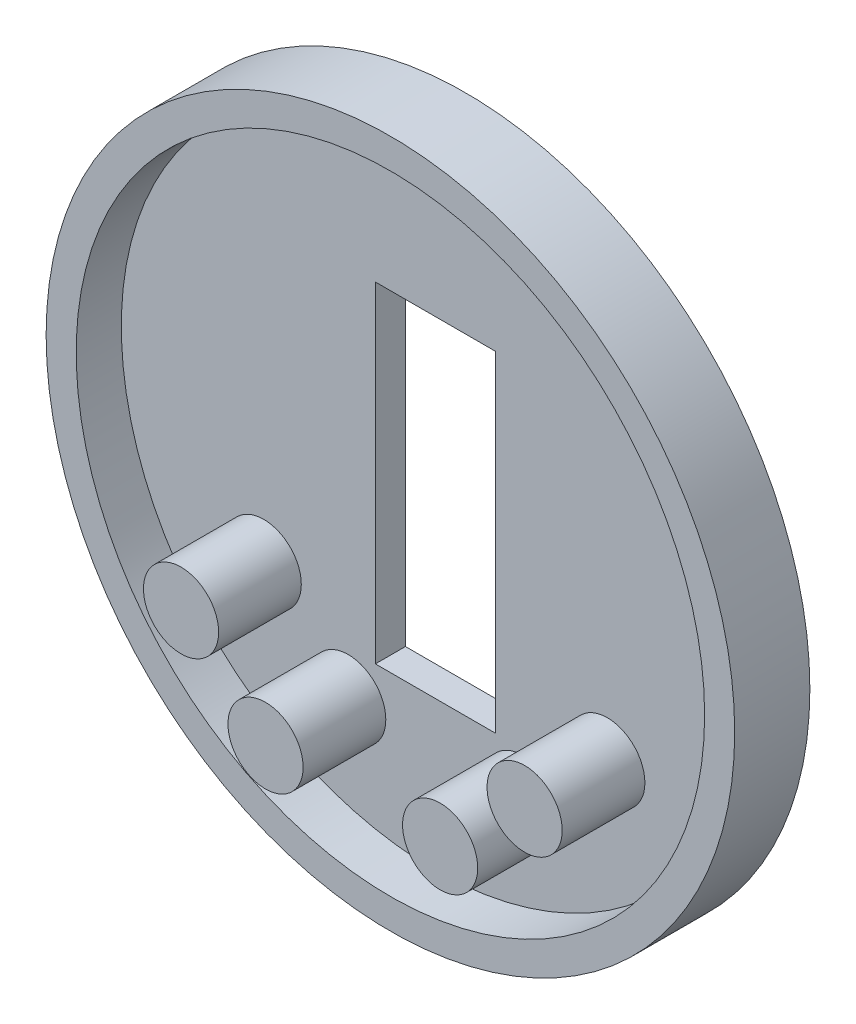
SolidWorks part; units mm, degrees
ref_plane "Ebene vorne" through (0, 0, 0) normal (0, 0, 1) x (1, 0, 0)
ref_plane "Ebene oben" through (0, 0, 0) normal (0, 1, 0) x (1, 0, 0)
ref_plane "Ebene rechts" through (0, 0, 0) normal (1, 0, 0) x (0, 0, -1)
sketch "Skizze1" plane through (0, 0, 0) normal (0, 1, 0) x (1, 0, 0)
  line L0 (0, 0) -> (22.902, 0)
  line L1 (22.902, 0) -> (22.902, -5)
  line L2 (22.902, -5) -> (20.902, -5)
  line L3 (20.902, -5) -> (20.902, -2)
  line L4 (20.902, -2) -> (0, -2)
  line L5 (0, -2) -> (0, 0)
revolve "Rotation2" add sketch "Skizze1" angle 360 about L5
sketch "Skizze2" plane through (0, 0, 0) normal (0, 0, -1) x (-1, 0, 0)
  line L0 (0, 0) -> (4, 0)
  line L4 (4, 11) -> (-4, 11)
  line L5 (-4, 11) -> (-4, -11)
  line L6 (4, 11) -> (4, -11)
  line L7 (4, -11) -> (-4, -11)
extrude "Schnitt-Linear austragen1" cut sketch "Skizze2" against normal blind 10 contours L7 L6 L4 L5 region at (-3.7659, 5.5, 0)
sketch "Skizze3" plane through (0, 0, 0) normal (0, 0, 1) x (1, 0, 0)
  line L0 (0, 0) -> (0, -8.885)
  line L1 (0, -13.863) -> (5.8065, -13.863)
  line L2 (0, -13.863) -> (-5.8065, -13.863)
  line L3 (0, -8.885) -> (-11.4275, -8.885)
  line L4 (0, -8.885) -> (11.4275, -8.885)
  circle A0 centre (-5.8065, -13.863) radius 2.5
  circle A1 centre (5.8065, -13.863) radius 2.5
  circle A2 centre (-11.4275, -8.885) radius 2.5
  circle A3 centre (11.4275, -8.885) radius 2.5
extrude "Aufsatz-Linear austragen1" add sketch "Skizze3" along normal blind 7.5 contours A3
extrude "Aufsatz-Linear austragen2" add sketch "Skizze3<5>" along normal blind 7.5 contours A1 region at (5.8065, -11.4337, 0)
sketch "Skizze3<5>" plane through (0, 0, 0) normal (0, 0, 1) x (1, 0, 0) same geometry as "Skizze3"
extrude "Aufsatz-Linear austragen3" add sketch "Skizze3<6>" along normal blind 7.5 contours A0 region at (-8.2358, -13.863, 0)
sketch "Skizze3<6>" plane through (0, 0, 0) normal (0, 0, 1) x (1, 0, 0) same geometry as "Skizze3"
extrude "Aufsatz-Linear austragen4" add sketch "Skizze3<7>" along normal blind 7.5 contours A2
sketch "Skizze3<7>" plane through (0, 0, 0) normal (0, 0, 1) x (1, 0, 0) same geometry as "Skizze3"
